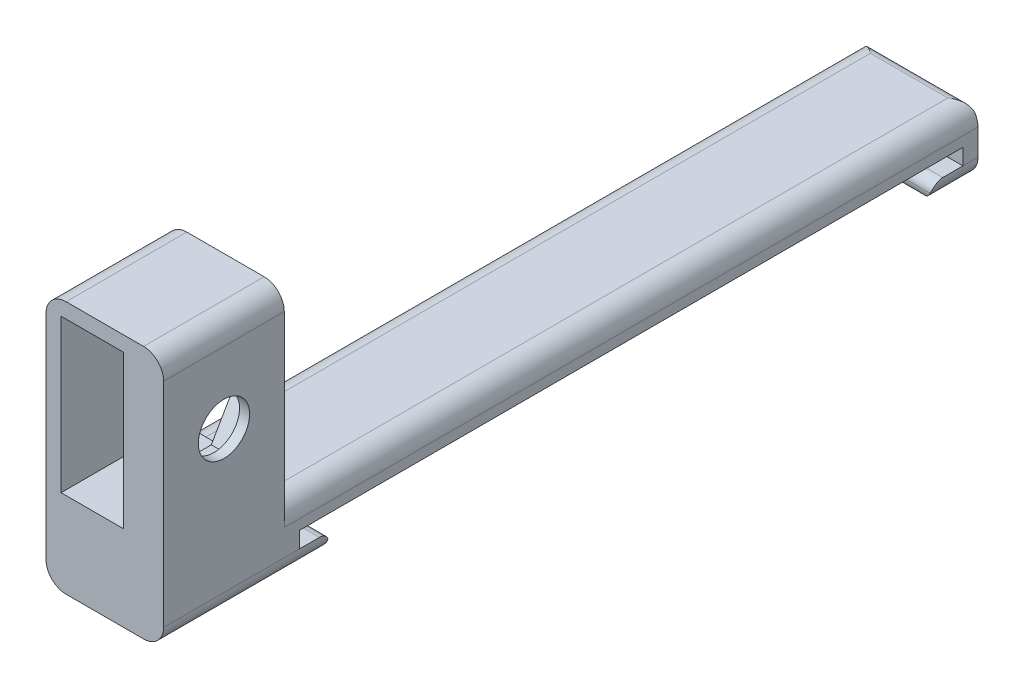
SolidWorks part; units mm, degrees
note: The reader was unsure of these and kept them because the rebuilt part matched: shared geometry of "Sketch4<3>".
ref_plane "Front Plane" through (0, 0, 0) normal (0, 0, 1) x (1, 0, 0)
ref_plane "Top Plane" through (0, 0, 0) normal (0, 1, 0) x (1, 0, 0)
ref_plane "Right Plane" through (0, 0, 0) normal (1, 0, 0) x (0, 0, -1)
sketch "Sketch1" plane through (0, 0, 0) normal (0, 0, 1) x (1, 0, 0)
  line L0 (0, 7.6) -> (0, 9.1) construction
  line L1 (-3.1, -7.6) -> (3.1, -7.6)
  line L2 (-3.1, -7.6) -> (-3.1, 7.6)
  line L3 (-3.1, 7.6) -> (3.1, 7.6)
  line L4 (3.1, -7.6) -> (3.1, 7.6)
  line L5 (-3.1, -7.6) -> (3.1, 7.6) construction
  line L6 (-3.1, 7.6) -> (3.1, -7.6) construction
  line L7 (-4.6, 9.1) -> (7.1, 9.1)
  line L8 (-4.6, 9.1) -> (-4.6, -9.1)
  line L9 (-4.6, -9.1) -> (7.1, -9.1)
  line L10 (7.1, 9.1) -> (7.1, -9.1)
  line L11 (0, -7.6) -> (0, -9.1) construction
  line L12 (3.1, 0) -> (7.1, 0) construction
  line L13 (-3.1, 0) -> (-4.6, 0) construction
  point P0 (0, 0)
  dimension "D1" = 4
  dimension "D2" = 1.5
  dimension "D3" = 6.2
  dimension "D4" = 15.2
extrude "Boss-Extrude1" add sketch "Sketch1" along normal blind 12
sketch "Sketch4" plane through (3.1, 0, 0) normal (-1, 0, 0) x (0, 0, 1)
  line L0 (0, 0) -> (12, 0) construction
  line L1 (0.5152, 0) -> (3.2576, -4.75)
  line L2 (3.2576, -4.75) -> (8.7424, -4.75)
  line L3 (8.7424, -4.75) -> (11.4848, 0)
  line L4 (11.4848, 0) -> (8.7424, 4.75)
  line L5 (8.7424, 4.75) -> (3.2576, 4.75)
  line L6 (3.2576, 4.75) -> (0.5152, 0)
  line L7 (0, -7.6) -> (0, 7.6) construction
  line L8 (12, -7.6) -> (12, 7.6) construction
  circle A0 centre (6, 0) radius 4.75 construction
  circle A1 centre (6, 0) radius 2.55
  point P15 (6, 0)
  dimension "D1" = 9.5
  dimension "D2" = 5.1
extrude "Cut-Extrude1" cut sketch "Sketch4" against normal blind 3
extrude "Cut-Extrude2" cut sketch "Sketch4<3>" against normal through all contours A1
sketch "Sketch4<3>" plane through (3.1, 0, 0) normal (-1, 0, 0) x (0, 0, 1) same geometry as "Sketch4"
sketch "Sketch9" plane through (0, -9.1, 0) normal (0, -1, 0) x (1, 0, 0)
  line L4 (-4.6, 0) -> (7.1, 0)
  line L5 (7.1, 0) -> (7.1, 12)
  line L6 (7.1, 12) -> (-4.6, 12)
  line L7 (-4.6, 12) -> (-4.6, 0)
  line L8 (-4.6, 0) -> (7.1, 0)
  line L9 (7.1, 0) -> (7.1, 12)
  line L10 (7.1, 12) -> (-4.6, 12)
  line L11 (-4.6, 12) -> (-4.6, 0)
  dimension "D1" = 0
extrude "Boss-Extrude4" add sketch "Sketch9" along normal blind 7
sketch "Sketch7" plane through (0, -2.9, 0) normal (0, 0, -1) x (1, 0, 0)
  line L0 (-4.6, 13.2) -> (7.1, 13.2) construction
  line L1 (7.1, 6.6) -> (-4.6, 6.6)
  line L2 (7.1, 6.6) -> (7.1, 13.2)
  line L3 (7.1, 13.2) -> (-4.6, 13.2)
  line L4 (-4.6, 6.6) -> (-4.6, 13.2)
  line L5 (7.1, -12) -> (-4.6, -12) construction
  line L6 (-4.6, -12) -> (-4.6, 13.2) construction
  point P6 (1.25, -12)
  point P11 (1.25, 6.6)
  dimension "D1" = 6.6
extrude "Boss-Extrude3" add sketch "Sketch7" along normal blind 69
sketch "Sketch10" plane through (7.1, 0, 0) normal (1, 0, 0) x (0, 0, -1)
  line L0 (64.5, -16.1) -> (64.5, -14.1)
  line L1 (69, -16.1) -> (-12, -16.1) construction
  line L2 (64.5, -14.1) -> (67.5, -14.1)
  line L3 (67.5, -14.1) -> (67.5, -12.5)
  line L4 (67.5, -12.5) -> (1.5, -12.5)
  line L5 (1.5, -12.5) -> (1.5, -14.1)
  line L6 (1.5, -14.1) -> (4.5, -14.1)
  line L7 (4.5, -14.1) -> (4.5, -16.1)
  line L8 (4.5, -16.1) -> (64.5, -16.1)
  line L9 (69, -9.5) -> (69, -16.1) construction
  dimension "D1" = 66
  dimension "D2" = 4.5
  dimension "D3" = 2
  dimension "D4" = 1.6
  dimension "D5" = 3
extrude "Cut-Extrude4" cut sketch "Sketch10" against normal through all
fillet "Fillet1" radius 2 8 edges at (7.1, 9.1, 6) (-4.6, 9.1, 6) (-4.6, -16.1, 3.75) (7.1, -16.1, 3.75) (7.1, -9.5, -34.5) (-4.6, -9.5, -34.5) (-4.6, -16.1, -66.75) (7.1, -16.1, -66.75)
fillet "Fillet2" radius 1 6 edges at (1.25, -14.1, -4.5) (1.25, -16.1, -4.5) (1.25, -9.5, -69) (1.25, -16.1, -69) (1.25, -14.1, -64.5) (1.25, -16.1, -64.5)
